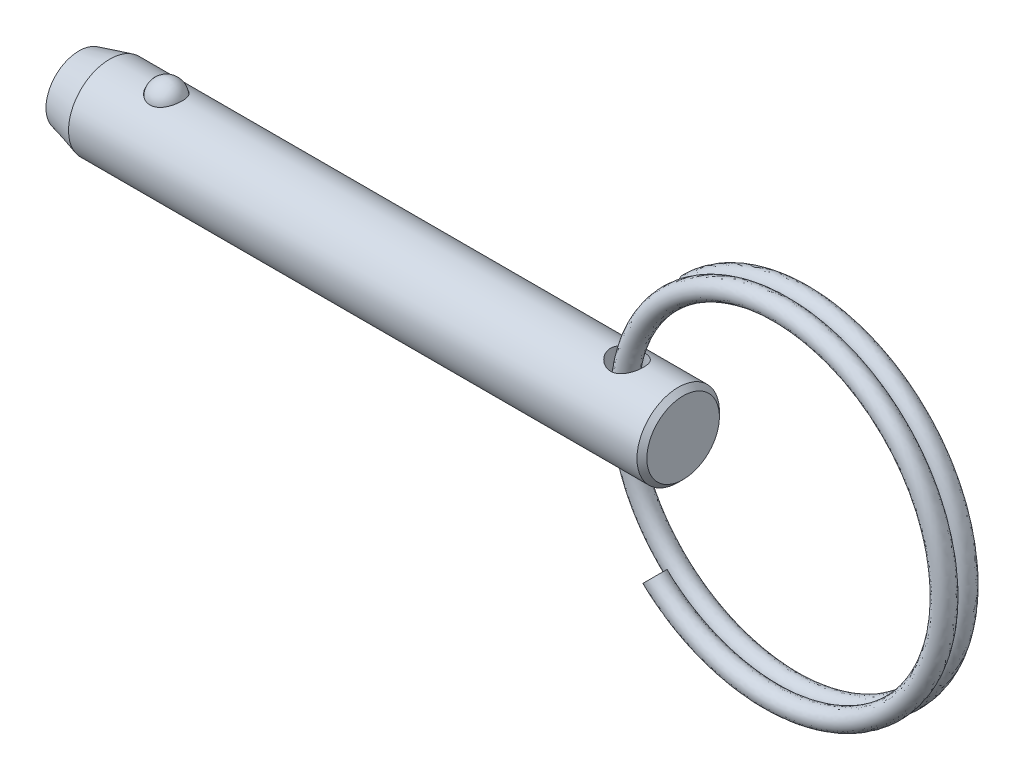
SolidWorks part; units mm, degrees
material "Plain Carbon Steel"
ref_plane "Front" through (0, 0, 0) normal (0, 0, 1) x (1, 0, 0)
ref_plane "Top" through (0, 0, 0) normal (0, 1, 0) x (1, 0, 0)
ref_plane "Right" through (0, 0, 0) normal (1, 0, 0) x (0, 0, -1)
sketch "Sketch1" plane through (0, 0, 0) normal (0, 0, 1) x (1, 0, 0)
  line L0 (23.2664, 2.794) -> (22.8854, 3.175)
  line L1 (22.8854, 3.175) -> (23.2664, 3.175) construction
  line L4 (23.2664, 2.794) -> (23.2664, 0)
  line L5 (23.2664, 3.175) -> (23.2664, 2.794) construction
  line L16 (22.8854, 3.175) -> (-20.8965, 3.175)
  line L17 (-23.2664, 3.175) -> (-23.2664, 2.54) construction
  line L19 (-20.8965, 3.175) -> (-23.2664, 3.175) construction
  line L22 (-23.2664, -3.175) -> (-20.8965, -3.175) construction
  line L23 (-16.5319, 2.8575) -> (-16.5319, -2.8575) construction
  line L24 (-23.2664, 0) -> (23.2664, 0)
  line L27 (23.2664, 0) -> (26.0604, 0) construction
  line L29 (-23.2664, 0) -> (-23.2664, -2.54) construction
  line L36 (17.6784, 0) -> (17.6784, 3.175) construction
  line L37 (-23.2664, 2.54) -> (-23.2664, 0)
  line L38 (-20.8965, -3.175) -> (23.2664, -3.175) construction
  line L39 (-23.2664, -2.54) -> (-23.2664, -3.175) construction
  line L40 (-20.8965, 3.175) -> (-23.2664, 2.54)
  line L42 (-20.8965, -3.175) -> (-23.2664, -2.54) construction
  line L43 (-20.8965, 3.175) -> (-20.8965, -3.175) construction
  circle A2 centre (-16.5319, 2.8575) radius 1.2319 construction
  point P35 (-15.3416, 3.175)
  dimension "A1" = 15
revolve "Revolve1" add sketch "Sketch1" angle 360 about L27
sketch "Sketch2" plane through (0, 0, 0) normal (0, 0, 1) x (1, 0, 0)
  line L0 (-15.2746, 2.8575) -> (-17.7892, 2.8575)
  line L1 (-16.5319, 4.0894) -> (-16.5319, 4.1148) construction
  line L2 (-15.2746, 2.8575) -> (-12.76, 2.8575) construction
  circle A0 centre (-16.5319, 2.8575) radius 1.2319 construction
  circle A1 centre (-16.5319, 2.8575) radius 1.2319 construction
  arc A2 (-17.7892, 2.8575) -> (-15.2746, 2.8575) centre (-16.5319, 2.8575) cw
  dimension "D1" = 0.0254
revolve "Cut-Revolve1" cut sketch "Sketch2" angle 360 about L2
sketch "Sketch3" plane through (0, 0, 0) normal (0, 0, 1) x (1, 0, 0)
  line L0 (-15.3, 2.8575) -> (-17.7638, 2.8575)
  line L1 (-15.3, 2.8575) -> (-12.8362, 2.8575) construction
  circle A0 centre (-16.5319, 2.8575) radius 1.2319 construction
  arc A1 (-15.3, 2.8575) -> (-17.7638, 2.8575) centre (-16.5319, 2.8575) ccw
revolve "Revolve2" add sketch "Sketch3" angle 360 about L1
sketch "Sketch4" plane through (0, 0, 0) normal (0, 0, 1) x (1, 0, 0)
  line L1 (18.9484, -3.175) -> (20.2184, -3.175)
  line L2 (18.9484, -3.175) -> (18.9484, 3.175)
  line L3 (18.9484, 3.175) -> (20.2184, 3.175)
  line L4 (20.2184, -3.175) -> (20.2184, 3.175)
  line L5 (18.9484, -3.175) -> (18.9484, -4.445) construction
  line L6 (20.2184, 3.175) -> (23.2664, 3.175) construction
  line L8 (17.6784, -3.175) -> (17.6784, 3.175) construction
  line L9 (17.6784, 0) -> (18.9484, 0) construction
  line L11 (18.9484, 0) -> (20.2184, 0) construction
  line L12 (22.8854, 3.175) -> (-20.8965, 3.175) construction
  line L14 (-20.8965, -3.175) -> (23.2664, -3.175) construction
  dimension "D1" = 2.54
revolve "Cut-Revolve2" cut sketch "Sketch4" angle 360 about L2
sketch "Sketch5" plane through (0, 0, 0) normal (0, 0, 1) x (1, 0, 0)
  line L0 (0, 0) -> (17.9714, 0) construction
  line L1 (17.9714, 0) -> (17.9714, 3.175) construction
  line L2 (22.8854, 3.175) -> (-20.8965, 3.175) construction
  line L3 (31.4334, 0) -> (44.8954, 0) construction
  line L4 (20.2184, 3.175) -> (19.9254, 3.175) construction
  line L5 (18.9484, 3.175) -> (20.2184, 3.175) construction
  line L6 (18.3512, 3.175) -> (18.3512, -3.175) construction
  line L7 (17.9714, 3.175) -> (17.6784, 3.175) construction
  line L8 (18.9484, -3.175) -> (20.2184, -3.175) construction
  line L9 (18.3512, -3.175) -> (20.2184, -3.175) construction
  line L10 (17.9714, 0) -> (31.4334, 0) construction
  line L12 (19.9254, 3.175) -> (18.3512, 3.175) construction
  line L13 (31.4334, 11.938) -> (31.4334, 13.462) construction
  circle A0 centre (31.4334, 0) radius 13.462
  circle A1 centre (31.4334, 0) radius 11.938 construction
  circle A2 centre (31.4334, 0) radius 12.7 construction
  point P26 (31.4334, 12.7)
curve "Helix/Spiral1" pitch 1.5494 height 1.3557 radius 13.462 left hand yes centre (31.4334, 0, 0) axis (0, 0, -1) start towards (1, 0, 0)
sketch "Sketch6" plane through (114.0038, 0, 0) normal (0, 1, 0) x (0, 0, -1)
  line L0 (0, 94.5084) -> (0, 95.2704) construction
  line L1 (0, 95.2704) -> (0, 96.0324) construction
  circle A0 centre (0, 95.2704) radius 0.762
  dimension "D1" = 1.524
sketch "Sketch7" plane through (0, 0, 0) normal (0, 0, 1) x (1, 0, 0)
  circle A0 centre (31.4334, 0) radius 13.462 construction
  circle A1 centre (31.4334, 0) radius 13.462
curve "Helix/Spiral2" pitch 1.5494 height 1.3557 radius 13.462 left hand yes centre (31.4334, 0, 0) axis (0, 0, 1) start towards (1, 0, 0)
sweep "Sweep1" add profiles "Sketch6" path "Helix/Spiral1"
sweep "Sweep2" add profiles "Sketch6<2>" path "Helix/Spiral2"
sketch "Sketch6<2>" plane through (114.0038, 0, 0) normal (0, 1, 0) x (0, 0, -1) same geometry as "Sketch6"
equation "\"D12@Sketch1\"=\"A@Sketch1\" * 0.80"
equation "\"D2@Sketch1\"=\"A@Sketch1\" * 0.9"
equation "\"D1@Sketch4\" = \"A@Sketch1\" / 2.5"
equation "\"Ring OD@Sketch5\" = \"R Ring Dia@Sketch5\" * 0.06"
equation "\"D4@Helix/Spiral1\"=\"Ring OD@Sketch5\" + 0.001"
equation "\"D1@Sketch6\"=\"Ring OD@Sketch5\""
equation "\"D4@Helix/Spiral2\" = \"D4@Helix/Spiral1\""
equation "\"D5@Helix/Spiral2\" = \"D5@Helix/Spiral1\""
